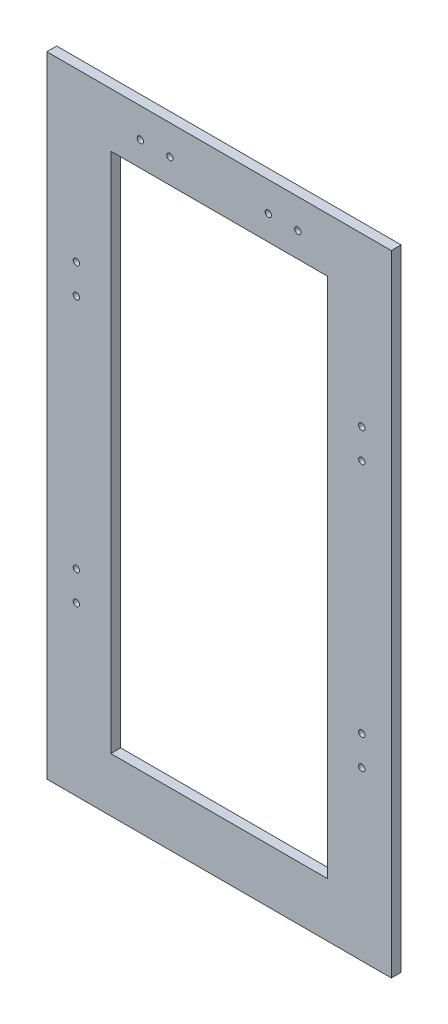
SolidWorks part; units mm, degrees
ref_plane "Front Plane" through (0, 0, 0) normal (0, 0, 1) x (1, 0, 0)
ref_plane "Top Plane" through (0, 0, 0) normal (0, 1, 0) x (1, 0, 0)
ref_plane "Right Plane" through (0, 0, 0) normal (1, 0, 0) x (0, 0, -1)
sketch "Sketch1" plane through (0, 0, 0) normal (0, 0, 1) x (1, 0, 0)
  line L1 (-87.5, -160) -> (87.5, -160)
  line L2 (-87.5, -160) -> (-87.5, 160)
  line L3 (-87.5, 160) -> (87.5, 160)
  line L4 (87.5, -160) -> (87.5, 160)
  line L5 (-87.5, -160) -> (87.5, 160) construction
  line L6 (-87.5, 160) -> (87.5, -160) construction
  point P0 (0, 0)
  dimension "D1" = 320
  dimension "D2" = 175
extrude "Boss-Extrude1" add sketch "Sketch1" along normal blind 5
sketch "Sketch2" plane through (0, 0, 0) normal (0, 0, -1) x (-1, 0, 0)
  line L1 (55, -132.5) -> (-55, -132.5)
  line L2 (55, -132.5) -> (55, 132.5)
  line L3 (55, 132.5) -> (-55, 132.5)
  line L4 (-55, -132.5) -> (-55, 132.5)
  line L5 (55, -132.5) -> (-55, 132.5) construction
  line L6 (55, 132.5) -> (-55, -132.5) construction
  point P0 (0, 0)
  dimension "D1" = 110
  dimension "D2" = 265
extrude "Cut-Extrude1" cut sketch "Sketch2" against normal up to next
sketch "Sketch4" plane through (0, 0, 0) normal (0, 0, -1) x (-1, 0, 0)
  line L0 (0, 160) -> (0, 145) construction
  line L2 (-87.5, 160) -> (87.5, 160) construction
  line L3 (0, 145) -> (-25, 145) construction
  line L4 (-25, 145) -> (-40, 145) construction
  circle A0 centre (-25, 145) radius 1.6
  circle A1 centre (-40, 145) radius 1.6
  circle A2 centre (25, 145) radius 1.6
  circle A3 centre (40, 145) radius 1.6
  dimension "D4" = 3.2
  dimension "D5" = 3.2
  dimension "D1" = 15
  dimension "D2" = 25
  dimension "D3" = 15
extrude "Cut-Extrude2" cut sketch "Sketch4" against normal up to next
sketch "Sketch5" plane through (0, 0, 0) normal (0, 0, -1) x (-1, 0, 0)
  line L0 (-87.5, 0) -> (-72.5, 0) construction
  line L1 (-87.5, -160) -> (-87.5, 160) construction
  line L2 (-72.5, 0) -> (-72.5, 60) construction
  line L3 (-72.5, 60) -> (-72.5, 75) construction
  line L5 (0, 0) -> (0, 19.1648) construction
  circle A0 centre (-72.5, 75) radius 1.6
  circle A1 centre (-72.5, 60) radius 1.6
  circle A2 centre (-72.5, -75) radius 1.6
  circle A3 centre (-72.5, -60) radius 1.6
  circle A4 centre (72.5, -75) radius 1.6
  circle A5 centre (72.5, -60) radius 1.6
  circle A6 centre (72.5, 60) radius 1.6
  circle A7 centre (72.5, 75) radius 1.6
  dimension "D2" = 3.2
  dimension "D3" = 3.2
  dimension "D1" = 15
  dimension "D4" = 15
  dimension "D5" = 60
extrude "Cut-Extrude3" cut sketch "Sketch5" against normal up to next
